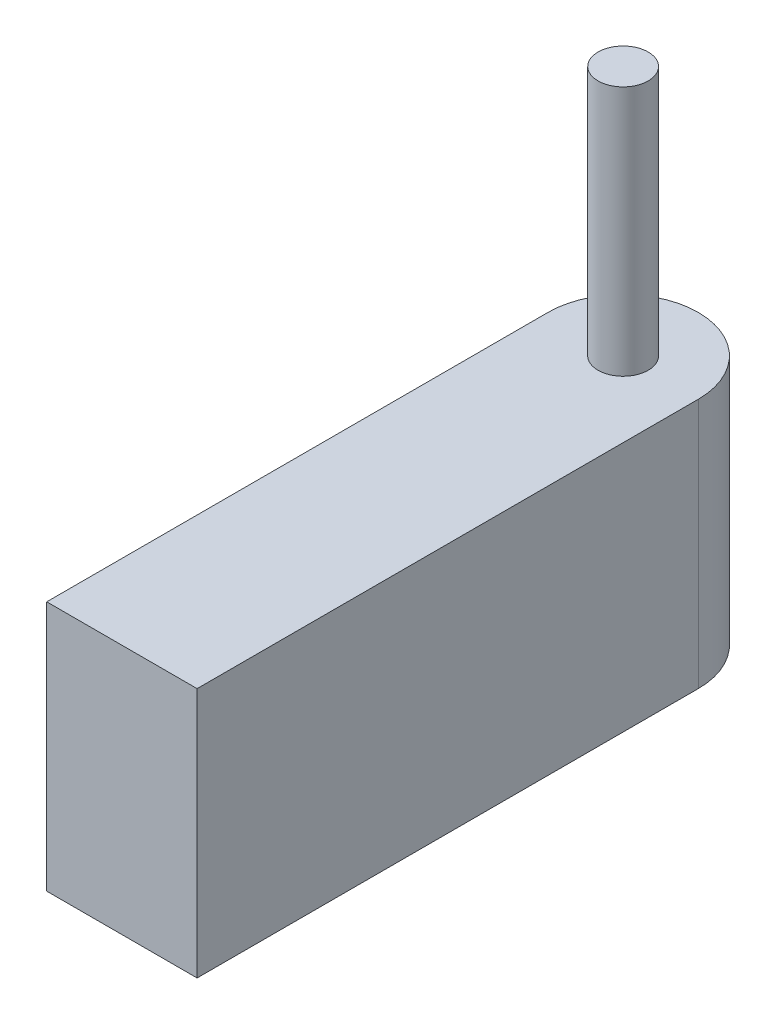
SolidWorks part; units mm, degrees
ref_plane "Front Plane" through (0, 0, 0) normal (0, 0, 1) x (1, 0, 0)
ref_plane "Top Plane" through (0, 0, 0) normal (0, 1, 0) x (1, 0, 0)
ref_plane "Right Plane" through (0, 0, 0) normal (1, 0, 0) x (0, 0, -1)
sketch "Sketch1" plane through (0, 0, 0) normal (0, 1, 0) x (1, 0, 0)
  line L1 (-0.381, -1.27) -> (0.381, -1.27)
  line L2 (-0.381, -1.27) -> (-0.381, 1.27)
  line L3 (-0.381, 1.27) -> (0.381, 1.27)
  line L4 (0.381, -1.27) -> (0.381, 1.27)
  line L5 (-0.381, -1.27) -> (0.381, 1.27) construction
  line L6 (-0.381, 1.27) -> (0.381, -1.27) construction
  circle A0 centre (0, 1.27) radius 0.381
  circle A1 centre (0, 1.27) radius 0.127
  point P0 (0, 0)
  dimension "D3" = 0.254
  dimension "D1" = 2.54
  dimension "D2" = 0.762
extrude "Boss-Extrude1" add sketch "Sketch1" along normal blind 1.27 contours A1 L3 A0 | L3 A1 | L3 A1 | A1 L3 A0 | A0 L2 L1 L4 region at (0, 0, 0.148) region at (0, 0, -1.4452) region at (0, 0, -1.0948) region at (0, 0, -1.3239) region at (0, 0, -1.2161)
extrude "Boss-Extrude2" add sketch "Sketch1<4>" along normal blind 2.54 contours L3 A1 | L3 A1 region at (0, 0, -1.3239) region at (0, 0, -1.2161)
sketch "Sketch1<4>" plane through (0, 0, 0) normal (0, 1, 0) x (1, 0, 0) same geometry as "Sketch1"
